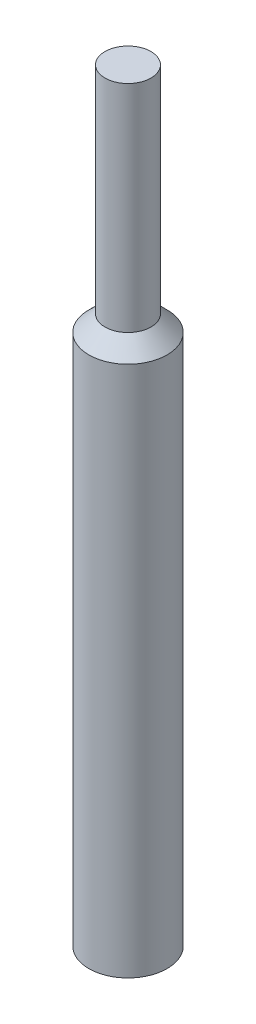
SolidWorks part; units mm, degrees
ref_plane "Front Plane" through (0, 0, 0) normal (0, 0, 1) x (1, 0, 0)
ref_plane "Top Plane" through (0, 0, 0) normal (0, 1, 0) x (1, 0, 0)
ref_plane "Right Plane" through (0, 0, 0) normal (1, 0, 0) x (0, 0, -1)
sketch "Sketch1" plane through (0, 0, 0) normal (0, 1, 0) x (1, 0, 0)
  circle A0 centre (0, 0) radius 6.35
  dimension "D1" = 12.7
extrude "Boss-Extrude1" add sketch "Sketch1" along normal blind 421.64
sketch "Sketch2" plane through (0, 0, 0) normal (0, -1, 0) x (-1, 0, 0)
  circle A0 centre (0, 0) radius 10.795
  dimension "D1" = 21.59
extrude "Boss-Extrude2" add sketch "Sketch2" against normal blind 421.64
sketch "Sketch3" plane through (0, 0, 0) normal (0, -1, 0) x (1, 0, 0)
  circle A0 centre (0, 0) radius 6.35
  circle A1 centre (0, 0) radius 25.4
  dimension "D1" = 12.7
  dimension "D2" = 50.8
extrude "Cut-Extrude1" cut sketch "Sketch3" against normal blind 52.324
sketch "Sketch4" plane through (0, 421.64, 0) normal (0, 1, 0) x (1, 0, 0)
  circle A0 centre (0, 0) radius 6.35
  circle A1 centre (0, 0) radius 25.4
  dimension "D1" = 50.8
  dimension "D2" = 12.7
extrude "Cut-Extrude2" cut sketch "Sketch4" against normal blind 57.658
ref_plane "Plane1" through (0, 210.82, 0) normal (0, 1, 0) x (1, 0, 0)
sketch "Sketch5" plane through (0, 210.82, 0) normal (0, 1, 0) x (1, 0, 0)
  circle A0 centre (0, 0) radius 15.875
  dimension "D1" = 31.75
chamfer "Chamfer1" distance 6.35 angle 45 2 edges at (0, 52.324, -10.795) (0, 363.982, 10.795)
extrude "Cut-Extrude3" cut sketch "Sketch5" against normal through all contours A0
sketch "Sketch6" plane through (0, 210.82, 0) normal (0, -1, 0) x (-1, 0, 0)
  line L1 (-5.0548, -3.2557) -> (0.2922, -6.0054)
  line L2 (0.2922, -6.0054) -> (5.3469, -2.7497)
  line L3 (5.3469, -2.7497) -> (5.0548, 3.2557)
  line L4 (5.0548, 3.2557) -> (-0.2922, 6.0054)
  line L5 (-0.2922, 6.0054) -> (-5.3469, 2.7497)
  line L6 (-5.3469, 2.7497) -> (-5.0548, -3.2557)
  circle A0 centre (0, 0) radius 5.207 construction
  dimension "D1" = 10.414
extrude "Cut-Extrude4" cut sketch "Sketch6" against normal blind 19.304
